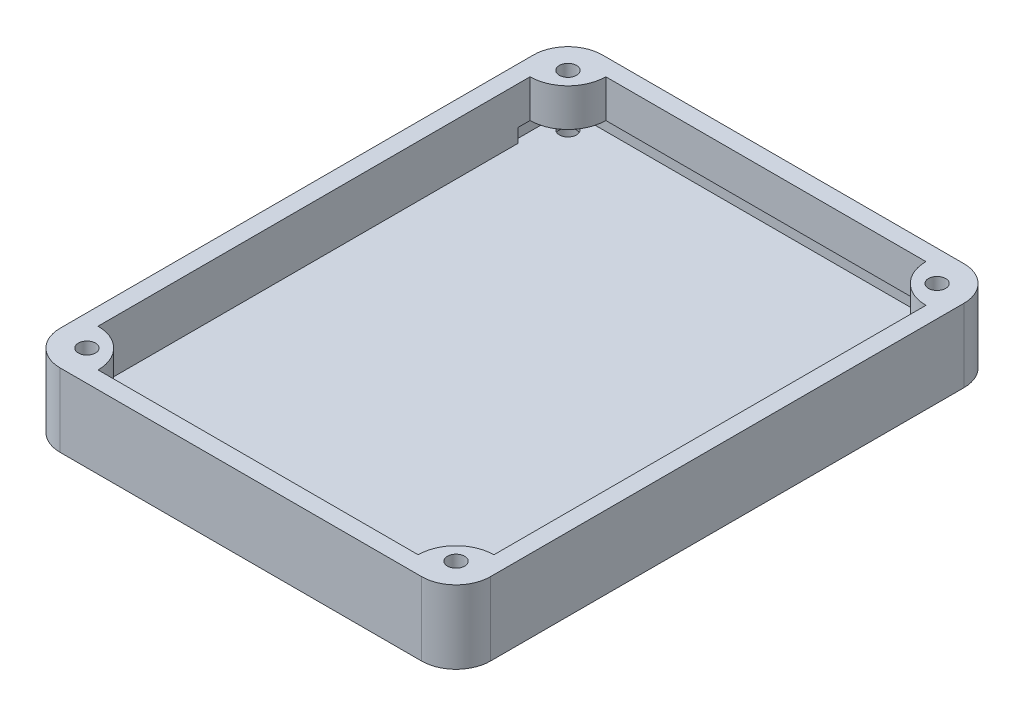
SolidWorks part; units mm, degrees
ref_plane "Front Plane" through (0, 0, 0) normal (0, 0, 1) x (1, 0, 0)
ref_plane "Top Plane" through (0, 0, 0) normal (0, 1, 0) x (1, 0, 0)
ref_plane "Right Plane" through (0, 0, 0) normal (1, 0, 0) x (0, 0, -1)
sketch "Sketch1" plane through (0, 0, 0) normal (0, 1, 0) x (1, 0, 0)
  line L1 (25, -31.5) -> (-25, -31.5)
  line L2 (25, -31.5) -> (25, 31.5)
  line L3 (25, 31.5) -> (-25, 31.5)
  line L4 (-25, -31.5) -> (-25, 31.5)
  line L5 (25, -31.5) -> (-25, 31.5) construction
  line L6 (25, 31.5) -> (-25, -31.5) construction
  line L7 (23, -29.5) -> (-23, -29.5)
  line L8 (23, -29.5) -> (23, 29.5)
  line L9 (23, 29.5) -> (-23, 29.5)
  line L10 (-23, -29.5) -> (-23, 29.5)
  line L11 (23, -29.5) -> (-23, 29.5) construction
  line L12 (23, 29.5) -> (-23, -29.5) construction
  point P0 (0, 0)
  point P6 (0, 0)
  dimension "D1" = 50
  dimension "D2" = 63
  dimension "D3" = 2
  dimension "D4" = 2
extrude "Boss-Extrude1" add sketch "Sketch1" along normal blind 6
sketch "Sketch2" plane through (0, 0, 0) normal (0, -1, 0) x (1, 0, 0)
  line L1 (-25, 31.5) -> (25, 31.5)
  line L2 (-25, 31.5) -> (-25, -31.5)
  line L3 (-25, -31.5) -> (25, -31.5)
  line L4 (25, 31.5) -> (25, -31.5)
  line L5 (-25, 31.5) -> (25, -31.5) construction
  line L6 (-25, -31.5) -> (25, 31.5) construction
  point P4 (0, 0)
extrude "Boss-Extrude2" add sketch "Sketch2" along normal blind 2.5
sketch "Sketch3" plane through (0, 0, 0) normal (0, 1, 0) x (1, 0, 0)
  line L0 (0, 31.5) -> (0, -31.5) construction
  line L1 (25, 31.5) -> (-25, 31.5) construction
  line L2 (-25, -31.5) -> (25, -31.5) construction
  line L3 (-23, 25.1) -> (-23, 29.5)
  line L4 (25, -31.5) -> (25, 31.5) construction
  line L5 (25, 0) -> (-25, 0) construction
  line L6 (-25, 31.5) -> (-25, -31.5) construction
  line L7 (-23, 29.5) -> (-23, -29.5) construction
  line L8 (23, 29.5) -> (-23, 29.5) construction
  line L9 (-23, 29.5) -> (-19.8887, 26.3887) construction
  line L10 (-23, 29.5) -> (-18.6, 29.5)
  line L11 (-23, 29.5) -> (-23, 25.1)
  line L12 (-18.6, 29.5) -> (-23, 29.5)
  line L13 (-23, 25.1) -> (-23, 29.5)
  line L14 (-23, 29.5) -> (-18.6, 29.5)
  line L15 (-23, 29.5) -> (-23, 25.1)
  line L16 (-18.6, 29.5) -> (-23, 29.5)
  line L17 (-23, 25.1) -> (-23, 29.5)
  line L18 (-23, 29.5) -> (-18.6, 29.5)
  line L19 (-23, 29.5) -> (-23, 25.1)
  line L20 (-18.6, 29.5) -> (-23, 29.5)
  line L21 (-23, 25.1) -> (-23, 29.5)
  line L22 (-23, 29.5) -> (-18.6, 29.5)
  line L23 (-23, 29.5) -> (-23, 25.1)
  line L24 (-18.6, 29.5) -> (-23, 29.5)
  line L25 (23, 29.5) -> (19.8887, 26.3887) construction
  line L26 (18.6, 29.5) -> (23, 29.5)
  line L27 (23, 29.5) -> (23, 25.1)
  line L28 (23, 29.5) -> (18.6, 29.5)
  line L29 (23, 25.1) -> (23, 29.5)
  line L30 (18.6, 29.5) -> (23, 29.5)
  line L31 (23, 29.5) -> (23, 25.1)
  line L32 (23, 29.5) -> (18.6, 29.5)
  line L33 (23, 25.1) -> (23, 29.5)
  line L34 (18.6, 29.5) -> (23, 29.5)
  line L35 (23, 29.5) -> (23, 25.1)
  line L36 (23, 29.5) -> (18.6, 29.5)
  line L37 (23, 25.1) -> (23, 29.5)
  line L38 (18.6, 29.5) -> (23, 29.5)
  line L39 (23, 29.5) -> (23, 25.1)
  line L40 (23, 29.5) -> (18.6, 29.5)
  line L41 (23, 25.1) -> (23, 29.5)
  line L42 (23, -29.5) -> (19.8887, -26.3887) construction
  line L43 (-23, -29.5) -> (-19.8887, -26.3887) construction
  line L44 (23, -25.1) -> (23, -29.5)
  line L45 (23, -29.5) -> (18.6, -29.5)
  line L46 (23, -29.5) -> (23, -25.1)
  line L47 (18.6, -29.5) -> (23, -29.5)
  line L48 (23, -25.1) -> (23, -29.5)
  line L49 (23, -29.5) -> (18.6, -29.5)
  line L50 (23, -29.5) -> (23, -25.1)
  line L51 (18.6, -29.5) -> (23, -29.5)
  line L52 (23, -25.1) -> (23, -29.5)
  line L53 (23, -29.5) -> (18.6, -29.5)
  line L54 (23, -29.5) -> (23, -25.1)
  line L55 (18.6, -29.5) -> (23, -29.5)
  line L56 (23, -25.1) -> (23, -29.5)
  line L57 (23, -29.5) -> (18.6, -29.5)
  line L58 (23, -29.5) -> (23, -25.1)
  line L59 (18.6, -29.5) -> (23, -29.5)
  line L60 (-18.6, -29.5) -> (-23, -29.5)
  line L61 (-23, -29.5) -> (-23, -25.1)
  line L62 (-23, -29.5) -> (-18.6, -29.5)
  line L63 (-23, -25.1) -> (-23, -29.5)
  line L64 (-18.6, -29.5) -> (-23, -29.5)
  line L65 (-23, -29.5) -> (-23, -25.1)
  line L66 (-23, -29.5) -> (-18.6, -29.5)
  line L67 (-23, -25.1) -> (-23, -29.5)
  line L68 (-18.6, -29.5) -> (-23, -29.5)
  line L69 (-23, -29.5) -> (-23, -25.1)
  line L70 (-23, -29.5) -> (-18.6, -29.5)
  line L71 (-23, -25.1) -> (-23, -29.5)
  line L72 (-18.6, -29.5) -> (-23, -29.5)
  line L73 (-23, -29.5) -> (-23, -25.1)
  line L74 (-23, -29.5) -> (-18.6, -29.5)
  line L75 (-23, -25.1) -> (-23, -29.5)
  arc A0 (-23, 25.1) -> (-18.6, 29.5) centre (-23, 29.5) ccw
  circle A1 centre (-21.4444, 27.9444) radius 1
  circle A3 centre (21.4444, 27.9444) radius 1
  arc A4 (23, 25.1) -> (18.6, 29.5) centre (23, 29.5) cw
  arc A7 (23, -25.1) -> (18.6, -29.5) centre (23, -29.5) ccw
  circle A8 centre (21.4444, -27.9444) radius 1
  circle A9 centre (-21.4444, -27.9444) radius 1
  arc A10 (-23, -25.1) -> (-18.6, -29.5) centre (-23, -29.5) cw
  line M3 (23, 29.5) -> (-23, 29.5)
  line M4 (-23, 29.5) -> (-23, -29.5)
  line M5 (-23, -29.5) -> (23, -29.5)
  line M6 (23, -29.5) -> (23, 29.5)
  dimension "D2" = 2
  dimension "D1" = 2.2
extrude "Boss-Extrude3" add sketch "Sketch3" along normal up to surface (6 mm away) contours A0 A1 M4 M3 | A4 A3 M6 M3 | A7 A8 M6 M5 | A10 A9 M4 M5 region at (-22.9378, 0, -27.3) region at (-19.9327, 0, 26.4327) region at (20.8, 0, -29.4378) region at (19.9327, 0, 26.4327) up to face at (0, 6, 0)
fillet "Fillet1" radius 4 4 edges at (25, 1.75, -31.5) (-25, 1.75, -31.5) (25, 1.75, 31.5) (-25, 1.75, 31.5)
sketch "Sketch4" plane through (0, 0, -31.5) normal (0, 0, -1) x (-1, 0, 0)
  line L0 (0, -2.5) -> (0, 12.3379) construction
  line L1 (-10.5, -1.5) -> (-13.5, -1.5)
  line L2 (-10.5, -1.5) -> (-10.5, 8.5)
  line L3 (-10.5, 8.5) -> (-13.5, 8.5)
  line L4 (-13.5, -1.5) -> (-13.5, 8.5)
  line L5 (-10.5, -1.5) -> (-13.5, 8.5) construction
  line L6 (-10.5, 8.5) -> (-13.5, -1.5) construction
  line L7 (21, -2.5) -> (-21, -2.5) construction
  point P4 (-12, 3.5)
  dimension "D1" = 12
  dimension "D2" = 10
  dimension "D3" = 3
  dimension "D4" = 6
extrude "Boss-Extrude4" [suppressed] add sketch "Sketch4" along normal blind 10
sketch "Sketch5" [suppressed] plane through (10.5, 0, 0) normal (-1, 0, 0) x (0, 0, 1)
  line L0 (-42, -0.2) -> (-42, 9.8) construction
  line L1 (-42, -0.2) -> (-32, -0.2) construction
  circle A0 centre (-39, 3.3) radius 1
  dimension "D3" = 2
  dimension "D1" = 3
  dimension "D2" = 3.5
extrude "Cut-Extrude1" [suppressed] cut sketch "Sketch5" against normal blind 1 contours A0
chamfer "Chamfer3" [suppressed] distance 5 angle 70
fillet "Fillet4" [suppressed] radius 2
mirror "Mirror8" [suppressed] about plane through (0, 0, 0) normal (1, 0, 0)
mirror "Mirror9" [suppressed] about plane through (0, 0, 0) normal (0, 0, 1)
sketch "Sketch6" plane through (-23, 0, 0) normal (1, 0, 0) x (0, 0, -1)
  line L0 (25.1, 3.2) -> (-25.1, 3.2) construction
  line L1 (18.9211, 1.2) -> (15.9211, 1.2)
  line L2 (18.9211, 1.2) -> (18.9211, 3.2)
  line L3 (18.9211, 3.2) -> (15.9211, 3.2)
  line L4 (15.9211, 1.2) -> (15.9211, 3.2)
  line L5 (18.9211, 1.2) -> (15.9211, 3.2) construction
  line L6 (18.9211, 3.2) -> (15.9211, 1.2) construction
  line L7 (1.5, 1.2) -> (-1.5, 1.2)
  line L8 (1.5, 1.2) -> (1.5, 3.2)
  line L9 (1.5, 3.2) -> (-1.5, 3.2)
  line L10 (-1.5, 1.2) -> (-1.5, 3.2)
  line L11 (1.5, 1.2) -> (-1.5, 3.2) construction
  line L12 (1.5, 3.2) -> (-1.5, 1.2) construction
  line L13 (-15.9211, 1.2) -> (-18.9211, 1.2)
  line L14 (-15.9211, 1.2) -> (-15.9211, 3.2)
  line L15 (-15.9211, 3.2) -> (-18.9211, 3.2)
  line L16 (-18.9211, 1.2) -> (-18.9211, 3.2)
  line L17 (-15.9211, 1.2) -> (-18.9211, 3.2) construction
  line L18 (-15.9211, 3.2) -> (-18.9211, 1.2) construction
  line L19 (25.1, 0) -> (-25.1, 0) construction
  line L20 (-25.1, 6) -> (-25.1, 0) construction
  line L21 (25.1, 6) -> (25.1, 0) construction
  line L22 (0, 3.2) -> (0, 1.2) construction
  line L23 (-17.4211, 2.2) -> (0, 2.2) construction
  line L24 (0, 2.2) -> (17.4211, 2.2) construction
  point P5 (17.4211, 2.2)
  point P9 (0, 2.2)
  point P14 (-17.4211, 2.2)
  point P28 (0, 3.2)
  dimension "D1" = 3.2
  dimension "D2" = 3
  dimension "D3" = 2
sketch "Sketch7" plane through (0, 0, 0) normal (0, 1, 0) x (1, 0, 0)
  line L0 (0, 31.5) -> (0, 15.0341) construction
  line L1 (21, 31.5) -> (-21, 31.5) construction
  line L2 (18.6, 29.5) -> (-18.6, 29.5) construction
  line L3 (22.5, 30) -> (-22.5, 30)
  line L5 (23.5, 23.7016) -> (-23.5, 23.7016)
  line L6 (-23.5, 29) -> (-23.5, 23.7016)
  line L7 (0, 30) -> (-23.5, 23.7016) construction
  line L9 (-23, 25.1) -> (-23, -25.1) construction
  line L11 (0, 30) -> (23.5, 23.7016) construction
  line L12 (23.5, 29) -> (23.5, 23.7016)
  arc A0 (22.5, 30) -> (23.5, 29) centre (22.5, 29) cw
  arc A1 (-23.5, 29) -> (-22.5, 30) centre (-22.5, 29) cw
  point P8 (-9.1425, 27.5496)
  point P15 (9.1425, 27.5496)
  dimension "D3" = 1
  dimension "D1" = 0.5
  dimension "D2" = 0.5
  dimension "D4" = 6.2984
extrude "Cut-Extrude3" cut sketch "Sketch7" along normal blind 1.6
extrude "Cut-Extrude7" cut sketch "Sketch3<5>" against normal blind 10 contours A9 | A8 | A3 | A1 region at (-21.4444, 0, -27.9444) region at (21.4444, 0, -27.9444) region at (21.4444, 0, 27.9444) region at (-21.4444, 0, 27.9444)
sketch "Sketch3<5>" plane through (0, 0, 0) normal (0, 1, 0) x (1, 0, 0) same geometry as "Sketch3"
sketch "Sketch10" plane through (0, -2.5, 0) normal (0, -1, 0) x (1, 0, 0)
  circle A0 centre (-21.4444, 27.9444) radius 2
  circle A1 centre (21.4444, 27.9444) radius 2
  circle A2 centre (21.4444, -27.9444) radius 2
  circle A3 centre (-21.4444, -27.9444) radius 2
  dimension "D1" = 4
extrude "Cut-Extrude10" cut sketch "Sketch10" against normal blind 2
